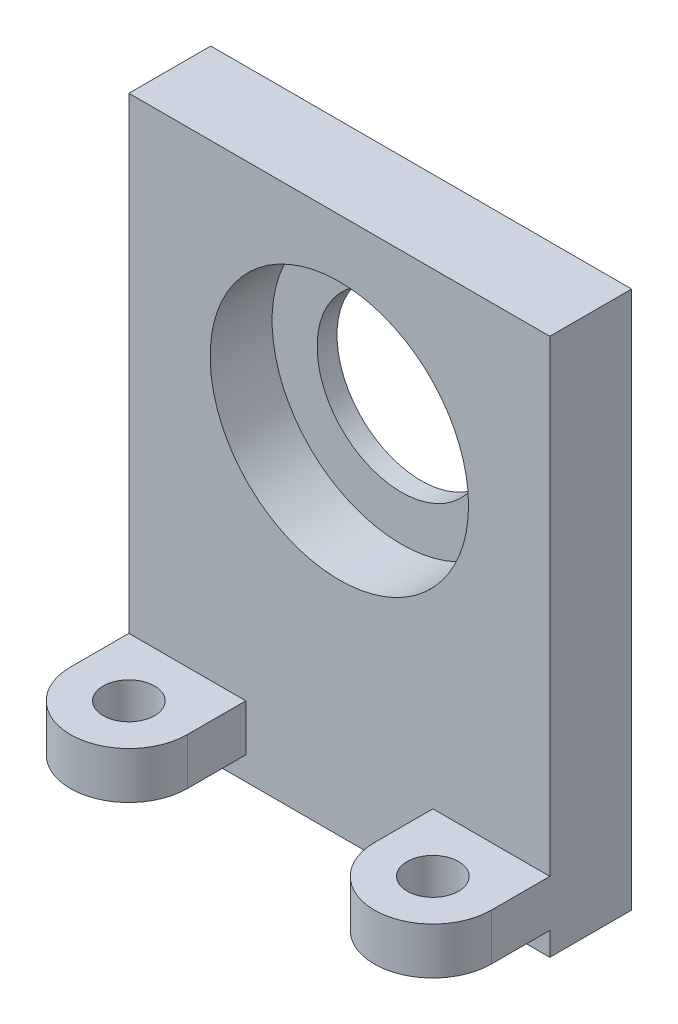
SolidWorks part; units mm, degrees
ref_plane "前视基准面" through (0, 0, 0) normal (0, 0, 1) x (1, 0, 0)
ref_plane "上视基准面" through (0, 0, 0) normal (0, 1, 0) x (1, 0, 0)
ref_plane "右视基准面" through (0, 0, 0) normal (1, 0, 0) x (0, 0, -1)
sketch "草图1" plane through (0, 0, 0) normal (0, 0, 1) x (1, 0, 0)
  line L1 (-9, 11) -> (9, 11)
  line L2 (-9, 11) -> (-9, -11)
  line L3 (-9, -11) -> (9, -11)
  line L4 (9, 11) -> (9, -11)
  line L5 (-9, 11) -> (9, -11) construction
  line L6 (-9, -11) -> (9, 11) construction
  point P0 (0, 0)
  dimension "D1" = 22
  dimension "D2" = 18
extrude "凸台-拉伸1" add sketch "草图1" along normal blind 3.5
sketch "草图2" plane through (0, 0, 3.5) normal (0, 0, 1) x (1, 0, 0)
  line L0 (0, -11) -> (0, 3) construction
  line L1 (-9, -11) -> (9, -11) construction
  circle A0 centre (0, 3) radius 3.6
  dimension "D2" = 7.2
  dimension "D1" = 14
extrude "切除-拉伸1" cut sketch "草图2" against normal blind 3.5
sketch "草图3" plane through (0, 0, 3.5) normal (0, 0, 1) x (1, 0, 0)
  circle A0 centre (0, 3) radius 5.525
  dimension "D1" = 11.05
extrude "切除-拉伸2" cut sketch "草图3" against normal blind 2.65
sketch "草图4" plane through (0, -11, 0) normal (0, -1, 0) x (1, 0, 0)
  line L1 (-9, 3.5) -> (-4, 3.5)
  line L2 (-9, 3.5) -> (-9, 8.5)
  line L3 (-9, 8.5) -> (-4, 8.5)
  line L4 (-4, 3.5) -> (-4, 8.5)
  dimension "D1" = 5
extrude "凸台-拉伸2" add sketch "草图4" against normal blind 2
fillet "圆角1" 2 edges at (-9, -10, 8.5) (-4, -10, 8.5) type full round first side face at (-9, -3, 4) second side face at (-4, -10, 6) middle face at (-6.5, -10, 8.5)
sketch "草图5" plane through (0, -9, 0) normal (0, 1, 0) x (1, 0, 0)
  circle A0 centre (-6.5, -6) radius 1.1
  dimension "D1" = 2.2
extrude "切除-拉伸3" cut sketch "草图5" against normal blind 3
ref_plane "基准面1" through (0, 0, 0) normal (-1, 0, 0) x (0, 0, 1)
mirror "镜向6" about plane through (0, 0, 0) normal (-1, 0, 0) of bodies 110
sketch "草图6" plane through (0, -11, 0) normal (0, -1, 0) x (1, 0, 0)
  line L1 (-9, 0) -> (9, 0)
  line L2 (-9, 0) -> (-9, 3.5)
  line L3 (-9, 3.5) -> (9, 3.5)
  line L4 (9, 0) -> (9, 3.5)
  line L5 (9, 6) -> (9, 0) construction
  dimension "D1" = 3.5
  dimension "D2" = 18
extrude "凸台-拉伸3" add sketch "草图6" along normal blind 1
